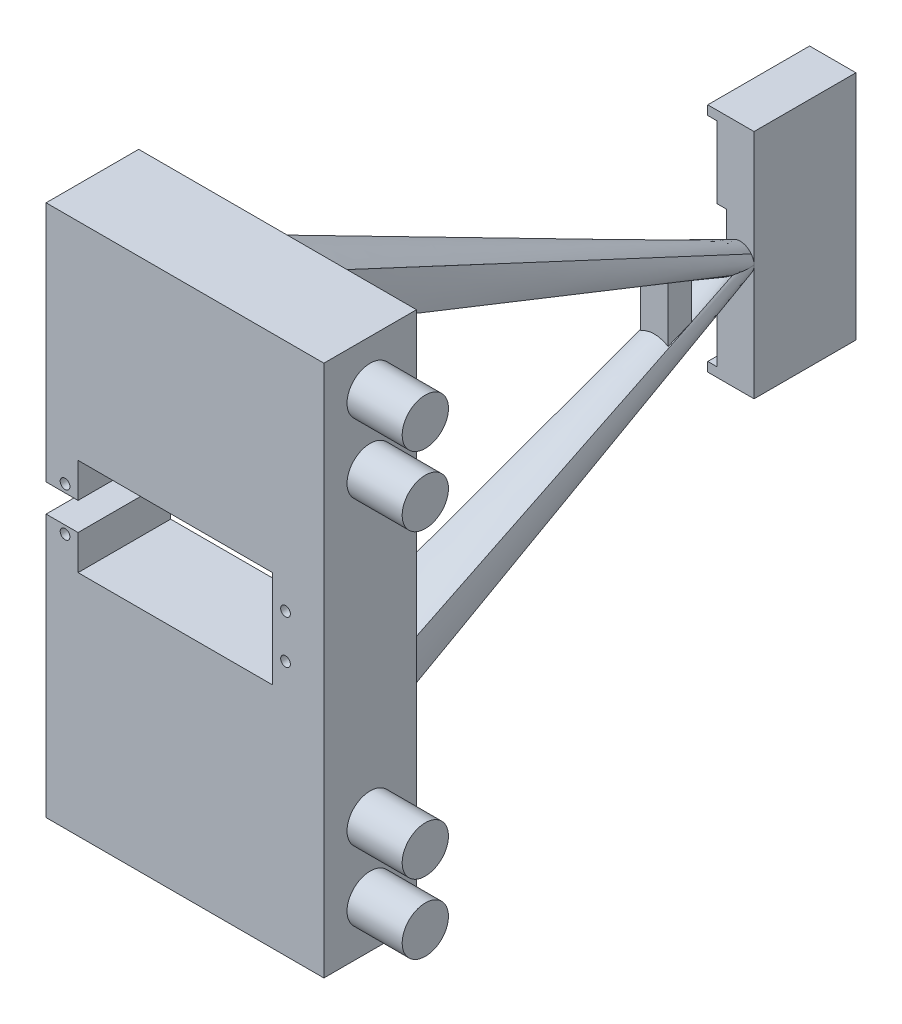
SolidWorks part; units mm, degrees
ref_plane "前基準面" through (0, 0, 0) normal (0, 0, 1) x (1, 0, 0)
ref_plane "上基準面" through (0, 0, 0) normal (0, 1, 0) x (1, 0, 0)
ref_plane "右基準面" through (0, 0, 0) normal (1, 0, 0) x (0, 0, -1)
sketch "草圖1" plane through (0, 0, 0) normal (0, 0, 1) x (1, 0, 0)
  line L0 (55, -3) -> (115, -3) construction
  line L5 (85, 54.5) -> (85, -60.5) construction
  line L6 (55, -3) -> (55, 0)
  line L7 (55, 0) -> (62, 0)
  line L8 (62, 0) -> (62, 7.5)
  line L9 (62, 7.5) -> (104, 7.5)
  line L10 (104, 7.5) -> (104, -13.5)
  line L11 (55, -6) -> (62, -6)
  line L12 (62, -6) -> (62, -13.5)
  line L13 (62, -13.5) -> (104, -13.5)
  line L14 (55, -3) -> (55, -6)
  circle A0 centre (59.19, 1.7) radius 1.05
  circle A1 centre (106.81, 1.7) radius 1.05
  circle A2 centre (106.81, -7.7) radius 1.05
  circle A3 centre (59.19, -7.7) radius 1.05
  point P18 (104, -3)
  dimension "D9" = 2.1
  dimension "D10" = 2.1
  dimension "D3" = 7
  dimension "D4" = 42
  dimension "D5" = 6
  dimension "D6" = 10.5
  dimension "D7" = 2.81
  dimension "D8" = 5.8
  dimension "D11" = 5.8
  dimension "D12" = 2.81
sketch "草圖5" plane through (0, 0, 0) normal (0, 0, 1) x (1, 0, 0)
  line L0 (62, 7.5) -> (104, 7.5) construction
  line L1 (55.0953, 52.2229) -> (115.0953, 52.2229)
  line L2 (55.0953, 52.2229) -> (55.0953, -62.7771)
  line L3 (55.0953, -62.7771) -> (115.0953, -62.7771)
  line L4 (115.0953, 52.2229) -> (115.0953, -62.7771)
  dimension "D1" = 115
  dimension "D2" = 60
  dimension "D3" = 44.7229
extrude "填料-伸長2" add sketch "草圖5" along normal blind 20
extrude "除料-伸長4" cut sketch "草圖1" along normal blind 20 contours L12 L13 L10 L9 L8 L7 L6 L14 L11 | A1 | A2 | A3 | A0
ref_plane "平面1" through (115, 0, 0) normal (1, 0, 0) x (0, 0, -1)
sketch "草圖6" plane through (115, 0, 0) normal (1, 0, 0) x (0, 0, -1)
  line L0 (-20, -5.2771) -> (0, -5.2771) construction
  line L1 (-20, -62.7771) -> (-20, 52.2229) construction
  line L2 (0, -62.7771) -> (0, 52.2229) construction
  line L3 (-10, 52.2229) -> (-10, -62.7771) construction
  line L4 (-20, 52.2229) -> (0, 52.2229) construction
  line L5 (-20, -62.7771) -> (0, -62.7771) construction
  circle A0 centre (-10, 42.2229) radius 5
  circle A1 centre (-10, 27.2229) radius 5
  circle A2 centre (-10, -37.7771) radius 5
  circle A3 centre (-10, -52.7771) radius 5
  dimension "D1" = 10
  dimension "D2" = 10
  dimension "D3" = 5
  dimension "D4" = 5
extrude "填料-伸長3" add sketch "草圖6" along normal blind 12
sketch "草圖8" plane through (0, 0, 0) normal (0, 0, 1) x (1, 0, 0)
  line L0 (85, 54.5) -> (85, -60.5) construction
  line L1 (91.8332, 47.8205) -> (78.1668, 47.8205)
  line L2 (91.8332, 47.8205) -> (91.8332, 37.5)
  line L3 (91.8332, 37.5) -> (78.1668, 37.5)
  line L4 (78.1668, 47.8205) -> (78.1668, 37.5)
  line L5 (115, -3) -> (55, -3) construction
  line L6 (91.8332, -43.5) -> (78.1668, -43.5)
  line L7 (78.1668, -53.8205) -> (78.1668, -43.5)
  line L8 (91.8332, -53.8205) -> (78.1668, -53.8205)
  line L9 (91.8332, -53.8205) -> (91.8332, -43.5)
  line L10 (62, 7.5) -> (104, 7.5) construction
  dimension "D1" = 30
ref_plane "平面2" through (0, 0, -100) normal (0, 0, 1) x (1, 0, 0)
sketch "草圖9" plane through (0, 0, -100) normal (0, 0, 1) x (1, 0, 0)
  line L0 (55, -3) -> (115, -3) construction
  line L1 (85, 21.0717) -> (85, -29.3934) construction
  line L2 (85, 54.5) -> (85, -60.5) construction
  circle A0 centre (85, -3) radius 3
  dimension "D1" = 6
surface "曲面-疊層拉伸7"
surface "曲面-疊層拉伸8"
sketch "草圖8<17>" plane through (0, 0, 0) normal (0, 0, 1) x (1, 0, 0) same geometry as "草圖8"
sketch "草圖9<10>" plane through (0, 0, -100) normal (0, 0, 1) x (1, 0, 0) same geometry as "草圖9"
ref_plane "平面3" through (82, 0, 0) normal (1, 0, 0) x (0, 0, -1)
sketch "草圖13" plane through (82, 0, 0) normal (1, 0, 0) x (0, 0, -1)
  line L0 (100, -3) -> (144.6975, -3) construction
  line L1 (100, 0) -> (100, -6) construction
  line L2 (122.3488, 28.2366) -> (122.3488, -29.5099) construction
  line L3 (100, 21.0717) -> (100, -29.3934) construction
  line L4 (122, 22) -> (100, 22)
  line L5 (122, 22) -> (122, -28)
  line L6 (122, -28) -> (100, -28)
  line L7 (100, 22) -> (100, -28)
  line L8 (111, 22) -> (111, -29.5099) construction
  dimension "D1" = 50
  dimension "D2" = 22
  dimension "D3" = 25
extrude "填料-伸長6" add sketch "草圖13" along normal blind 6 and the other way blind 4 separate body contours L5 L6 L7 L4
ref_plane "平面4" through (78, 0, 0) normal (1, 0, 0) x (0, 0, -1)
sketch "草圖16" plane through (78, 0, 0) normal (1, 0, 0) x (0, 0, -1)
  line L0 (122, -3) -> (100, -3) construction
  line L1 (122, 22) -> (122, -28) construction
  line L2 (100, 0) -> (100, -6) construction
  line L3 (100, 21.0717) -> (100, -29.3934) construction
  line L4 (120, 20) -> (100, 20)
  line L5 (120, 20) -> (120, -26)
  line L6 (120, -26) -> (100, -26)
  line L7 (100, 20) -> (100, -26)
  line L8 (110, 20) -> (110, -26) construction
  dimension "D1" = 46
  dimension "D2" = 20
  dimension "D3" = 23
  dimension "D4" = 10
extrude "除料-伸長9" cut sketch "草圖16" along normal blind 2 contours L5 L6 L7 L4
sketch "草圖17" plane through (78, 0, 0) normal (1, 0, 0) x (0, 0, -1)
  line L0 (100, -3) -> (122, -3) construction
  line L1 (100, 0) -> (100, -6) construction
  line L2 (122, 22) -> (122, -28) construction
  line L3 (100, 21.0717) -> (100, -29.3934) construction
  line L4 (105, 4.5) -> (100, 4.5)
  line L5 (105, 4.5) -> (105, -10.5)
  line L6 (105, -10.5) -> (100, -10.5)
  line L7 (100, 4.5) -> (100, -10.5)
  dimension "D1" = 15
  dimension "D2" = 5
  dimension "D3" = 7.5
extrude "除料-伸長10" cut sketch "草圖17" along normal blind 4
sketch "草圖18" plane through (82, 0, 0) normal (1, 0, 0) x (0, 0, -1)
  line L0 (86.4374, 0.9302) -> (86.4374, -6.9302)
  line L1 (0, 37.5) -> (100, -4.8079) construction
  line L2 (100, -1.1921) -> (0, -43.5) construction
  line L3 (81.442, 3.0436) -> (81.442, -9.0436)
  line L4 (86.4374, 0.9302) -> (81.442, 3.0436)
  line L5 (81.442, -9.0436) -> (86.4374, -6.9302)
extrude "填料-伸長7" add sketch "草圖18" along normal blind 6 separate body
